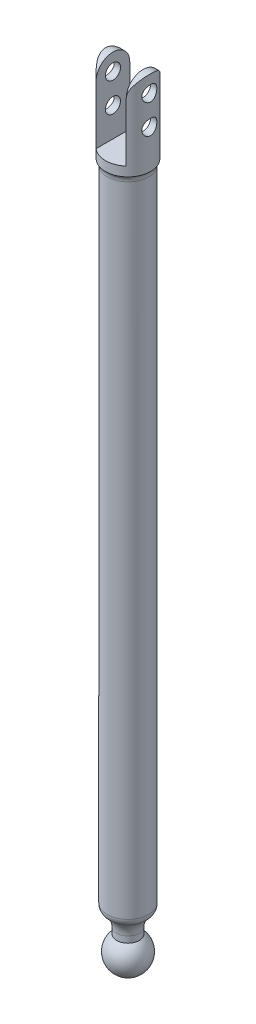
SolidWorks part; units mm, degrees
ref_plane "Front Plane" through (0, 0, 0) normal (0, 0, 1) x (1, 0, 0)
ref_plane "Top Plane" through (0, 0, 0) normal (0, 1, 0) x (1, 0, 0)
ref_plane "Right Plane" through (0, 0, 0) normal (1, 0, 0) x (0, 0, -1)
sketch "Esboço1" plane through (0, 0, 0) normal (0, 0, 1) x (1, 0, 0)
  line L0 (-10, 0) -> (10, 0) construction
  line L1 (-10, 0) -> (10, 0)
  arc A0 (10, 0) -> (-10, 0) centre (0, 0) ccw
  dimension "D1" = 20
revolve "Revolução1" add sketch "Esboço1" angle 360 about L0
sketch "Esboço2" plane through (0, 0, 0) normal (0, 1, 0) x (1, 0, 0)
  circle A0 centre (0, 0) radius 6
  dimension "D1" = 12
extrude "Ressalto-extrusão1" add sketch "Esboço2" along normal blind 20
sketch "Esboço3" plane through (0, 20, 0) normal (0, 1, 0) x (1, 0, 0)
  circle A0 centre (0, 0) radius 11
  dimension "D1" = 22
extrude "Ressalto-extrusão2" add sketch "Esboço3" along normal blind 350
fillet "Filete1" radius 10 1 edges at (0, 20, 6)
fillet "Filete2" radius 5 1 edges at (0, 20, 11)
sketch "Esboço4" plane through (0, 0, 0) normal (0, 0, 1) x (1, 0, 0)
  line L0 (0, 0) -> (0, 223.6213) construction
sketch "Esboço5" plane through (0, 370, 0) normal (0, 1, 0) x (1, 0, 0)
  line L0 (-8, 0) -> (6.7525, 0) construction
  line L4 (-8, -8.9443) -> (-8, 8.9443)
  line L5 (8, -8.9443) -> (8, 8.9443)
  line L7 (0, -8.7935) -> (0, 6.9875) construction
  arc A2 (-8, 8.9443) -> (-8, -8.9443) centre (0, 0) ccw
  arc A3 (8, -8.9443) -> (8, 8.9443) centre (0, 0) ccw
  point P0 (-8, 0)
  point P5 (8, -8.7935)
  point P11 (8, -8.7935)
  dimension "D1" = 8
  dimension "D2" = 24
  dimension "D3" = 8
extrude "Ressalto-extrusão3" add sketch "Esboço5" along normal blind 40
sketch "Esboço7" plane through (0, 370, 0) normal (0, 1, 0) x (1, 0, 0)
  circle A0 centre (0, 0) radius 12
extrude "Ressalto-extrusão4" add sketch "Esboço7" against normal blind 5
fillet "Filete3" radius 5 1 edges at (0, 365, 11)
sketch "Esboço8" plane through (0, 0, 0) normal (0, 0, 1) x (1, 0, 0)
  line L0 (-12, 410) -> (12, 365) construction
  line L1 (12, 365) -> (12, 410) construction
  line L2 (0, 377.5) -> (0, 397.5)
  arc A0 (0, 397.5) -> (0, 377.5) centre (0, 387.5) ccw
  dimension "D1" = 20
revolve "Corte-Revolução1" [suppressed] cut sketch "Esboço8" angle 360 about L2
sketch "Esboço9" plane through (0, 0, 0) normal (1, 0, 0) x (0, 0, -1)
  line L1 (-8.9443, 401.0557) -> (-8.9443, 410)
  line L2 (-8.9443, 410) -> (8.9443, 410)
  line L3 (8.9443, 410) -> (8.9443, 401.0557)
  arc A0 (8.9443, 401.0557) -> (-8.9443, 401.0557) centre (0, 401.0557) ccw
extrude "Corte-extrusão1" cut sketch "Esboço9" against normal mid plane 35 contours A0 L2 L1 | A0 L3 L2 region at (0, 408.0021, -6.9464) region at (0, 408.0021, 6.9464)
sketch "Esboço10" plane through (8, 0, 0) normal (-1, 0, 0) x (0, 0, 1)
  line L0 (8.9443, 370) -> (0, 401.0557) construction
  line L1 (0, 401.0557) -> (-8.9443, 370) construction
  line L2 (0, 401.0557) -> (0, 370) construction
  line L3 (8.9443, 370) -> (-8.9443, 370) construction
  circle A0 centre (0, 385.5279) radius 4
  circle A1 centre (0, 401.0557) radius 4
  dimension "D1" = 8
  dimension "D2" = 8
extrude "Corte-extrusão2" cut sketch "Esboço10" against normal up to body and the other way up to surface separate body other way up to face at (0, 365, 12)
